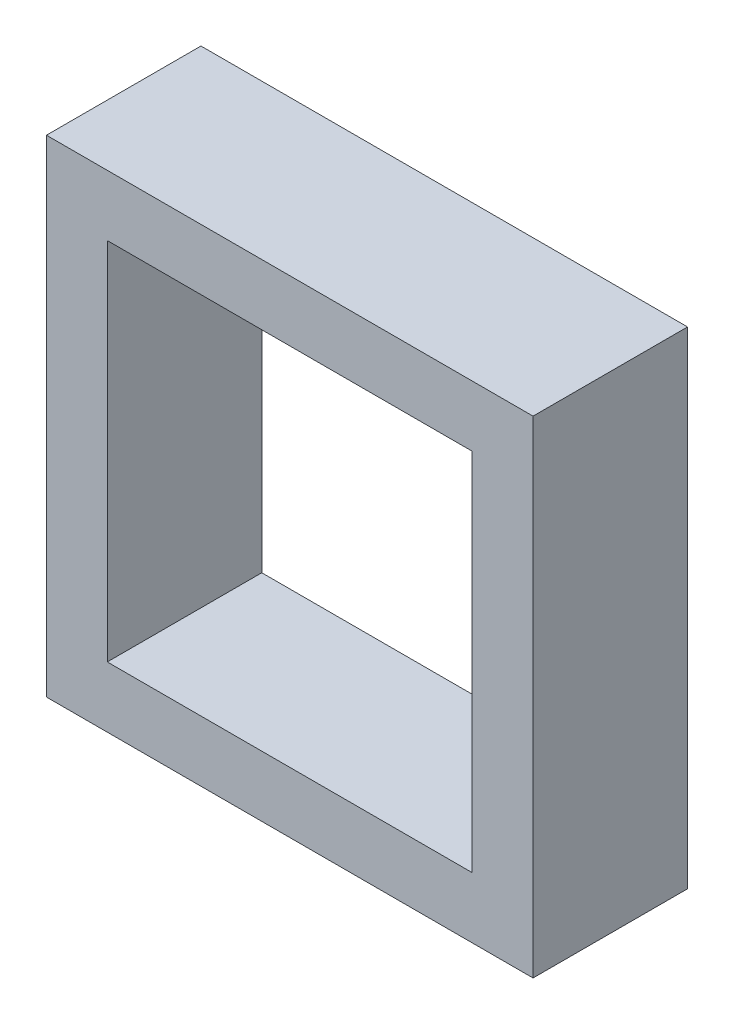
SolidWorks part; units mm, degrees
ref_plane "Front Plane" through (0, 0, 0) normal (0, 0, 1) x (1, 0, 0)
ref_plane "Top Plane" through (0, 0, 0) normal (0, 1, 0) x (1, 0, 0)
ref_plane "Right Plane" through (0, 0, 0) normal (1, 0, 0) x (0, 0, -1)
sketch "Sketch1" plane through (0, 0, 0) normal (0, 0, 1) x (1, 0, 0)
  line L0 (-15.2353, 17.8836) -> (-15.2353, 2.8836)
  line L1 (-15.2353, 2.8836) -> (-0.2353, 2.8836)
  line L2 (-0.2353, 2.8836) -> (-0.2353, 17.8836)
  line L3 (-0.2353, 17.8836) -> (2.2647, 17.8836)
  line L4 (2.2647, 17.8836) -> (2.2647, 0.3836)
  line L5 (2.2647, 0.3836) -> (-17.7353, 0.3836)
  line L6 (-17.7353, 0.3836) -> (-17.7353, 17.8836)
  line L7 (-17.7353, 17.8836) -> (-15.2353, 17.8836)
  dimension "D1" = 2.5
  dimension "D2" = 15
  dimension "D3" = 2.5
  dimension "D4" = 15
  dimension "D5" = 15
  dimension "D6" = 2.5
extrude "Boss-Extrude1" add sketch "Sketch1" along normal blind 6.35
sketch "Sketch2" plane through (0, 0, 0) normal (0, 0, 1) x (1, 0, 0)
  line L5 (-17.7353, 17.8836) -> (2.2647, 17.8836)
  line L6 (-17.7353, 17.8836) -> (-17.7353, 20.3836)
  line L7 (-17.7353, 20.3836) -> (2.2647, 20.3836)
  line L8 (2.2647, 17.8836) -> (2.2647, 20.3836)
  dimension "D1" = 20
  dimension "D2" = 2.5
extrude "Boss-Extrude2" add sketch "Sketch2" along normal through all
